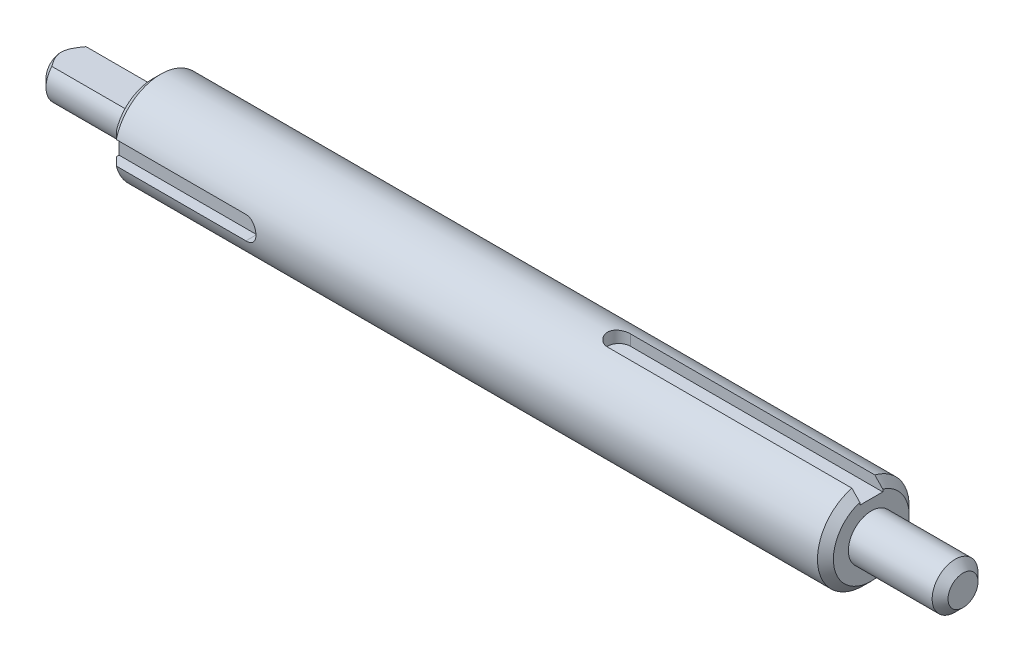
SolidWorks part; units mm, degrees
material "Stainless Steel (ferritic)"
ref_plane "Front Plane" through (0, 0, 0) normal (0, 0, 1) x (1, 0, 0)
ref_plane "Top Plane" through (0, 0, 0) normal (0, 1, 0) x (1, 0, 0)
ref_plane "Right Plane" through (0, 0, 0) normal (1, 0, 0) x (0, 0, -1)
sketch "Sketch1" plane through (0, 0, 0) normal (0, 0, 1) x (1, 0, 0)
  line L8 (0, 0) -> (0, 9.525)
  line L9 (0, 9.525) -> (149.225, 9.525)
  line L10 (149.225, 9.525) -> (149.225, 4.7625)
  line L11 (149.225, 4.7625) -> (168.275, 4.7625)
  line L12 (168.275, 4.7625) -> (168.275, 0)
  line L13 (0, 0) -> (168.275, 0)
  dimension "D1" = 4.7625
  dimension "D2" = 9.525
  dimension "D3" = 149.225
  dimension "D4" = 19.05
revolve "Revolve1" add sketch "Sketch1" angle 360 about L13
sketch "Sketch2" plane through (0, 0, 0) normal (-1, 0, 0) x (0, 0, 1)
  line L0 (-3.5498, 3.175) -> (3.5498, 3.175)
  arc A0 (-3.5498, 3.175) -> (3.5498, 3.175) centre (0, 0) ccw
  dimension "D1" = 9.525
  dimension "D2" = 3.175
extrude "Boss-Extrude1" add sketch "Sketch2" along normal blind 19.05
chamfer "Chamfer1" distance 1.651 angle 45 4 edges at (168.275, 0, 4.7625) (149.225, 0, 9.525) (0, 0, 9.525) (-19.05, -4.7625, 0)
sketch "Sketch4" plane through (0, 0, 0) normal (0, 0, 1) x (1, 0, 0)
  line L0 (0, 2.3813) -> (0, -2.3813)
  line L1 (0, 7.874) -> (0, -7.874) construction
  line L2 (0, -2.3813) -> (28.575, -2.3813)
  line L3 (0, 2.3813) -> (28.575, 2.3813)
  arc A0 (28.575, -2.3813) -> (28.575, 2.3813) centre (28.575, 0) ccw
  dimension "D3" = 28.575
  dimension "D1" = 4.7625
  dimension "D2" = 2.3813
extrude "Cut-Extrude1" cut sketch "Sketch4" along normal blind 19.05 from offset 6.985
sketch "Sketch5" plane through (0, 0, 0) normal (0, 1, 0) x (1, 0, 0)
  line L0 (149.225, 2.3812) -> (149.225, -2.3812)
  line L1 (149.225, -4.7625) -> (149.225, 4.7625) construction
  line L2 (149.225, -7.874) -> (149.225, 7.874) construction
  line L3 (149.225, -2.3812) -> (96.8248, -2.3812)
  line L4 (149.225, 2.3812) -> (96.8248, 2.3812)
  arc A0 (96.8248, 2.3812) -> (96.8248, -2.3812) centre (96.8248, 0) ccw
  point P6 (149.225, 0)
  dimension "D2" = 52.4002
  dimension "D1" = 4.7625
extrude "Cut-Extrude2" cut sketch "Sketch5" along normal blind 19.05 from offset 6.985
